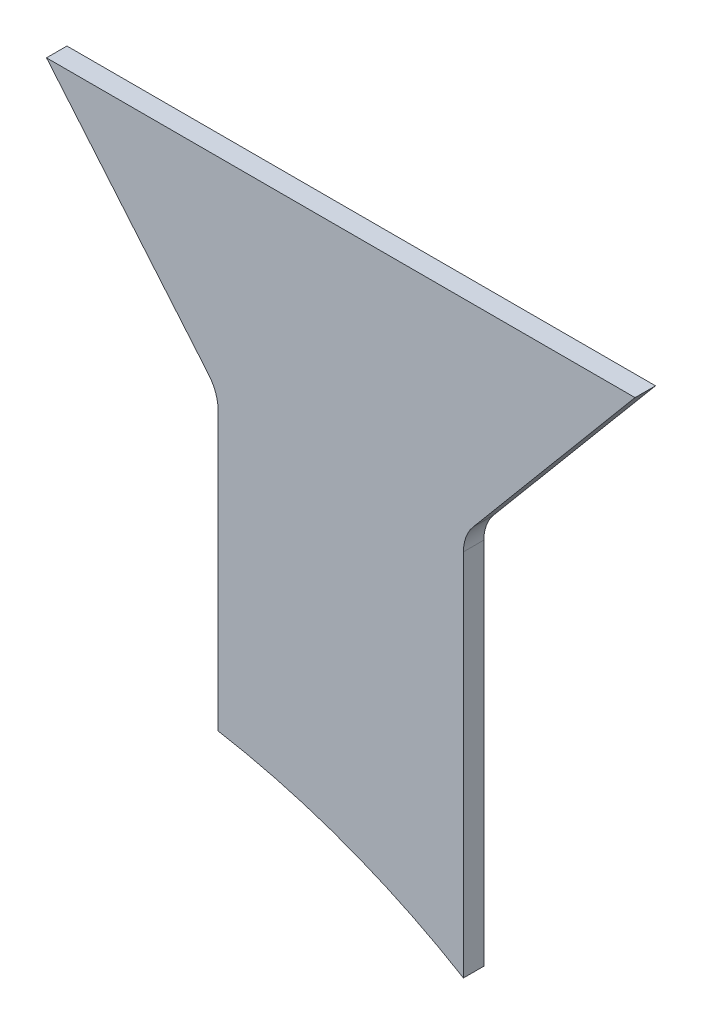
SolidWorks part; units mm, degrees
material "201 Annealed Stainless Steel (SS)"
ref_plane "Front Plane" through (0, 0, 0) normal (0, 0, 1) x (1, 0, 0)
ref_plane "Top Plane" through (0, 0, 0) normal (0, 1, 0) x (1, 0, 0)
ref_plane "Right Plane" through (0, 0, 0) normal (1, 0, 0) x (0, 0, -1)
sketch "Sketch1" plane through (0, 0, 0) normal (0, 0, 1) x (1, 0, 0)
  line L1 (30, 0) -> (30, 93.9)
  line L2 (30, 93.9) -> (71.974, 143.9227)
  line L6 (0, 0) -> (30, 0) construction
  line L7 (0, 0) -> (0, 143.9227) construction
  line L8 (-71.974, 143.9227) -> (71.974, 143.9227)
  line L9 (-30, 22.3261) -> (-30, 93.9)
  line L10 (-30, 93.9) -> (-71.974, 143.9227)
  line L11 (0, 0) -> (0, -123.071) construction
  line L12 (-60, -150.0833) -> (44.1454, -150.0833) construction
  line L13 (-30, 0) -> (-30, 22.3261) construction
  line L14 (-30, 0) -> (0, 0) construction
  line L15 (-30, 22.3261) -> (-30, -94.1356) construction
  line L16 (30, 0) -> (30, -97.0815) construction
  arc A1 (30, 0) -> (-30, 22.3261) centre (-60, -150.0833) ccw
  circle A2 centre (-60, -150.0833) radius 175 construction
  dimension "D5" = 175
  dimension "D6" = 90
  dimension "D1" = 30
  dimension "D2" = 140
  dimension "D3" = 65.3
  dimension "D4" = 93.9
extrude "Funnel - Side Panel" add sketch "Sketch1" along normal blind 5
fillet "Fillet1" radius 10 2 edges at (-30, 93.9, 2.5) (30, 93.9, 2.5)
